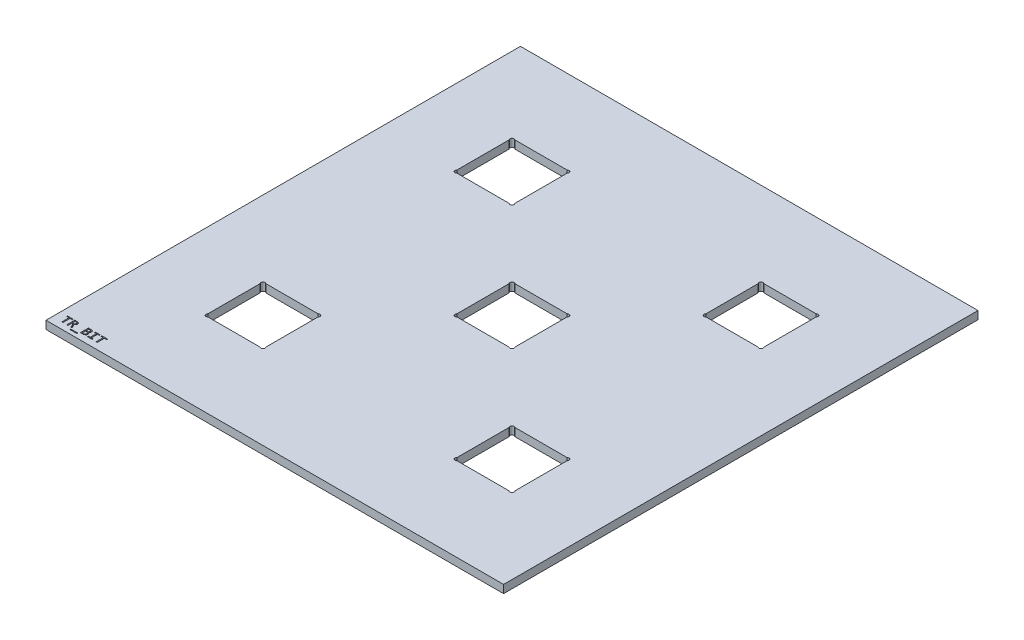
SolidWorks part; units mm, degrees
ref_plane "Front" through (0, 0, 0) normal (0, 0, 1) x (1, 0, 0)
ref_plane "Top" through (0, 0, 0) normal (0, 1, 0) x (1, 0, 0)
ref_plane "Right" through (0, 0, 0) normal (1, 0, 0) x (0, 0, -1)
sketch "Sketch1" plane through (0, 0, 0) normal (0, 1, 0) x (1, 0, 0)
  line L1 (-90.424, -93.7578) -> (90.424, -93.7578)
  line L2 (-90.424, -93.7578) -> (-90.424, 93.7578)
  line L3 (-90.424, 93.7578) -> (90.424, 93.7578)
  line L4 (90.424, -93.7578) -> (90.424, 93.7578)
  line L5 (-90.424, -93.7578) -> (90.424, 93.7578) construction
  line L6 (-90.424, 93.7578) -> (90.424, -93.7578) construction
  point P0 (0, 0)
  dimension "D1" = 180.848
  dimension "D2" = 187.5155
extrude "Boss-Extrude1" add sketch "Sketch1" along normal blind 3.175
sketch "Sketch2" plane through (0, 3.175, 0) normal (0, 1, 0) x (1, 0, 0)
  line L0 (-90.424, 93.7578) -> (90.424, -93.7578) construction
  line L2 (-11.43, -11.43) -> (11.43, -11.43)
  line L3 (-11.43, -11.43) -> (-11.43, 11.43)
  line L4 (-11.43, 11.43) -> (11.43, 11.43)
  line L5 (11.43, -11.43) -> (11.43, 11.43)
  line L6 (-11.43, -11.43) -> (11.43, 11.43) construction
  line L7 (-11.43, 11.43) -> (11.43, -11.43) construction
  point P4 (0, 0)
  point P10 (0, 0)
  dimension "D1" = 22.86
extrude "Cut-Extrude1" cut sketch "Sketch2" against normal blind 3.175
sketch "Sketch3" plane through (0, 3.175, 0) normal (0, 1, 0) x (1, 0, 0)
  line L0 (-11.43, 11.43) -> (-10.3075, 11.43) construction
  line L1 (11.43, 11.43) -> (-11.43, 11.43) construction
  line L2 (-11.43, 11.43) -> (-11.43, 10.3075) construction
  line L3 (11.43, 11.43) -> (11.43, 10.3075) construction
  line L4 (11.43, 11.43) -> (10.3075, 11.43) construction
  line L5 (11.43, -11.43) -> (10.3075, -11.43) construction
  line L6 (11.43, -11.43) -> (11.43, -10.3075) construction
  line L7 (-11.43, -11.43) -> (-11.43, -10.3075) construction
  line L8 (-11.43, -11.43) -> (-10.3075, -11.43) construction
  line L9 (11.43, -11.43) -> (-11.43, 11.43) construction
  circle A0 centre (-10.8687, 10.8687) radius 0.7937
  circle A1 centre (10.8687, 10.8687) radius 0.7938
  circle A2 centre (10.8687, -10.8687) radius 0.7938
  circle A3 centre (-10.8687, -10.8687) radius 0.7938
  point P8 (0, 0)
  point P9 (0, 0)
  point P28 (0, 0)
  dimension "D1" = 1.5875
  dimension "D2" = 4
extrude "Cut-Extrude2" cut sketch "Sketch3" against normal through all
sketch "Sketch8" plane through (0, 3.175, 0) normal (0, 1, 0) x (1, 0, 0)
  line L0 (90.424, -93.7578) -> (-90.424, 93.7578) construction
  line L2 (49.2125, 49.2125) -> (-49.2125, 49.2125) construction
  line L3 (49.2125, 49.2125) -> (49.2125, -49.2125) construction
  line L4 (49.2125, -49.2125) -> (-49.2125, -49.2125) construction
  line L5 (-49.2125, 49.2125) -> (-49.2125, -49.2125) construction
  line L6 (49.2125, 49.2125) -> (-49.2125, -49.2125) construction
  line L7 (49.2125, -49.2125) -> (-49.2125, 49.2125) construction
  point P4 (0, 0)
  point P11 (-49.2125, -49.2125)
  point P12 (-49.2125, 49.2125)
  point P13 (49.2125, 49.2125)
  point P14 (49.2125, -49.2125)
  dimension "D1" = 98.425
pattern_sketch "Sketch-Pattern1" of "Cut-Extrude1", "Cut-Extrude2" driven by "Sketch8"
sketch "Sketch4" plane through (0, 3.175, 0) normal (0, 1, 0) x (1, 0, 0)
  line L0 (-87.884, -91.2177) -> (90.424, -91.2177) construction
  line L1 (-90.424, -93.7578) -> (-87.884, -93.7578) construction
  line L2 (-90.424, -93.7578) -> (-90.424, -91.2177) construction
  line L3 (-90.424, -91.2177) -> (-87.884, -91.2177) construction
  line L4 (-87.884, -93.7578) -> (-87.884, -91.2177) construction
  line L5 (90.424, -93.7578) -> (90.424, 93.7578) construction
  text T0 "TR_BIT" font "Consolas" height 3.175
  dimension "D1" = 2.54
extrude "Cut-Extrude3" cut sketch "Sketch4" against normal blind 1.5875
